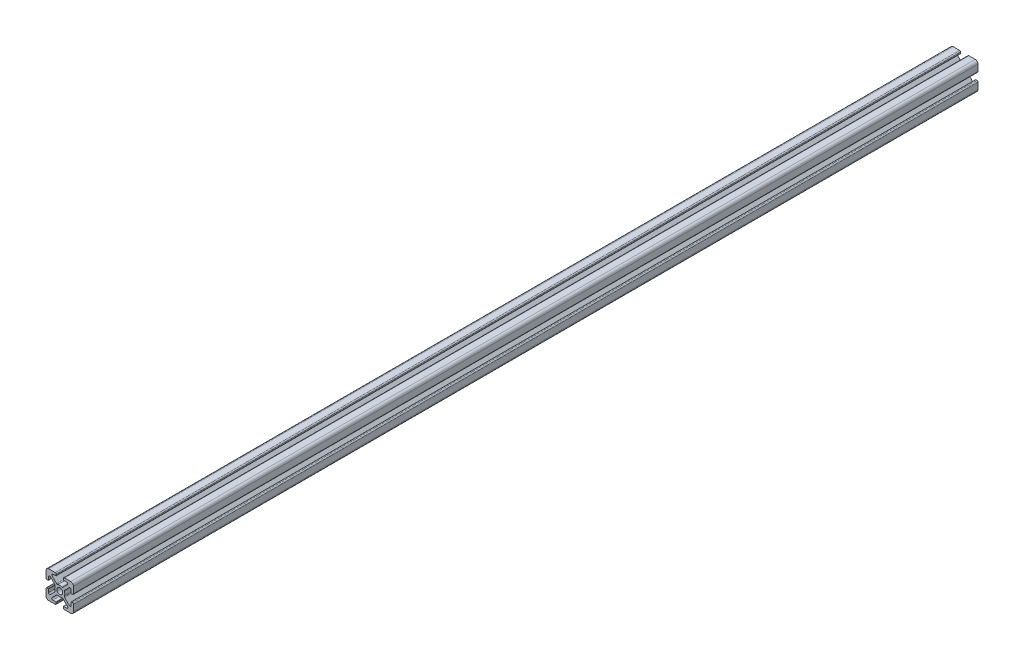
SolidWorks part; units mm, degrees
material "1060 Alloy"
ref_plane "Front Plane" through (0, 0, 0) normal (0, 0, 1) x (1, 0, 0)
ref_plane "Top Plane" through (0, 0, 0) normal (0, 1, 0) x (1, 0, 0)
ref_plane "Right Plane" through (0, 0, 0) normal (1, 0, 0) x (0, 0, -1)
sketch "PROFILE - DND" plane through (0, 0, 0) normal (0, 0, 1) x (1, 0, 0)
  line L0 (-5.0456, 8.2) -> (-2.825, 8.2)
  line L1 (-8, 10) -> (-3.3544, 10)
  line L5 (-10, 10) -> (0, 0) construction
  line L6 (-10, 10) -> (11.2313, -11.2313) construction
  line L15 (-5.5967, 6.8695) -> (-2.2618, 3.5346)
  line L18 (-9.3636, 10.6364) -> (11.8677, -10.5949) construction
  line L19 (0, 3.65) -> (0, 2.15)
  line L20 (-10, 8) -> (-10, 3.3544)
  line L21 (-9.2206, 2.575) -> (-8.45, 2.575)
  line L26 (-10, 8.2) -> (3.2269, 8.2) construction
  line L27 (-10, 8.2) -> (-22.2752, 8.2) construction
  line L28 (-22.2752, 8.2) -> (8.212, -7.6348) construction
  line L29 (3.2269, 8.2) -> (8.212, -7.6348) construction
  line L30 (-10, 0) -> (-3.65, 0) construction
  line L31 (0, 10) -> (0, 3.65) construction
  line L32 (-2.575, 9.2206) -> (-2.575, 8.45)
  line L37 (-2.575, 10) -> (-2.575, -10) construction
  line L39 (-8.2, 2.825) -> (-8.2, 5.0456)
  line L42 (-29.646, 10) -> (11.2313, -11.2313) construction
  line L44 (-10, 10) -> (4.5474, 10) construction
  line L47 (-10, 10) -> (-29.646, 10) construction
  line L50 (-6.8695, 5.5967) -> (-3.5346, 2.2618)
  line L55 (4.5474, 10) -> (11.2313, -11.2313) construction
  line L56 (0, 10) -> (0, -10) construction
  line L57 (-3.65, 0) -> (-2.15, 0)
  arc A0 (0, 2.15) -> (-2.15, 0) centre (0, 0) ccw
  arc A1 (0, 3.65) -> (-1.4097, 3.3668) centre (0, 0) ccw
  arc A3 (-5.5967, 6.8695) -> (-5.0456, 8.2) centre (-5.0456, 7.4206) cw
  arc A4 (-8.2, 5.0456) -> (-6.8695, 5.5967) centre (-7.4206, 5.0456) cw
  arc A5 (-2.2618, 3.5346) -> (-1.4097, 3.3668) centre (-1.7107, 4.0857) ccw
  arc A6 (-3.5346, 2.2618) -> (-3.3668, 1.4097) centre (-4.0857, 1.7107) cw
  arc A7 (-8, 10) -> (-10, 8) centre (-8, 8) ccw
  arc A8 (-2.575, 9.2206) -> (-3.3544, 10) centre (-3.3544, 9.2206) ccw
  arc A9 (-10, 3.3544) -> (-9.2206, 2.575) centre (-9.2206, 3.3544) ccw
  arc A10 (-2.575, 8.45) -> (-2.825, 8.2) centre (-2.825, 8.45) cw
  arc A11 (-8.45, 2.575) -> (-8.2, 2.825) centre (-8.45, 2.825) ccw
  arc A12 (-3.3668, 1.4097) -> (-3.65, 0) centre (0, 0) ccw
  point P71 (-5.825, 7.4206)
  dimension "D3" = 4.3
  dimension "D9" = 0.7794
  dimension "D10" = 2
  dimension "D13" = 0.25
  dimension "D2" = 7.3
  dimension "D4" = 6.35
  dimension "D5" = 5.15
  dimension "D6" = 11.65
  dimension "D8" = 1.8
  dimension "D7" = 20
  dimension "D1" = 1.8
sketch "Sketch2" plane through (0, 0, 0) normal (0, 0, 1) x (1, 0, 0)
  line L25 (-5.0456, 8.2) -> (-2.825, 8.2) construction
  line L26 (-2.575, 9.2206) -> (-2.575, 8.45) construction
  line L27 (-8, 10) -> (-3.3544, 10) construction
  line L28 (-10, 8) -> (-10, 3.3544) construction
  line L29 (-9.2206, 2.575) -> (-8.45, 2.575) construction
  line L30 (-8.2, 2.825) -> (-8.2, 5.0456) construction
  line L31 (-6.8695, 5.5967) -> (-3.5346, 2.2618) construction
  line L33 (-3.65, 0) -> (-2.15, 0) construction
  line L34 (0, 3.65) -> (0, 2.15) construction
  line L36 (-5.5967, 6.8695) -> (-2.2618, 3.5346) construction
  line L37 (-5.0456, 8.2) -> (-2.825, 8.2)
  line L38 (-2.575, 9.2206) -> (-2.575, 8.45)
  line L39 (-8, 10) -> (-3.3544, 10)
  line L40 (-10, 8) -> (-10, 3.3544)
  line L41 (-9.2206, 2.575) -> (-8.45, 2.575)
  line L42 (-8.2, 2.825) -> (-8.2, 5.0456)
  line L43 (-6.8695, 5.5967) -> (-3.5346, 2.2618)
  line L45 (-3.65, 0) -> (-2.15, 0)
  line L46 (0, 3.65) -> (0, 2.15)
  line L48 (-5.5967, 6.8695) -> (-2.2618, 3.5346)
  arc A0 (0, 3.65) -> (-1.4097, 3.3668) centre (0, 0) ccw construction
  arc A1 (-3.3668, 1.4097) -> (-3.65, 0) centre (0, 0) ccw construction
  arc A2 (0, 3.65) -> (-1.4097, 3.3668) centre (0, 0) ccw
  arc A3 (-3.3668, 1.4097) -> (-3.65, 0) centre (0, 0) ccw
  arc A20 (-5.0456, 8.2) -> (-5.5967, 6.8695) centre (-5.0456, 7.4206) ccw construction
  arc A21 (-2.825, 8.2) -> (-2.575, 8.45) centre (-2.825, 8.45) ccw construction
  arc A22 (-2.575, 9.2206) -> (-3.3544, 10) centre (-3.3544, 9.2206) ccw construction
  arc A23 (-8, 10) -> (-10, 8) centre (-8, 8) ccw construction
  arc A24 (-10, 3.3544) -> (-9.2206, 2.575) centre (-9.2206, 3.3544) ccw construction
  arc A25 (-8.45, 2.575) -> (-8.2, 2.825) centre (-8.45, 2.825) ccw construction
  arc A26 (-6.8695, 5.5967) -> (-8.2, 5.0456) centre (-7.4206, 5.0456) ccw construction
  arc A27 (-3.3668, 1.4097) -> (-3.5346, 2.2618) centre (-4.0857, 1.7107) ccw construction
  arc A28 (0, 2.15) -> (-2.15, 0) centre (0, 0) ccw construction
  arc A29 (-2.2618, 3.5346) -> (-1.4097, 3.3668) centre (-1.7107, 4.0857) ccw construction
  arc A30 (-5.0456, 8.2) -> (-5.5967, 6.8695) centre (-5.0456, 7.4206) ccw
  arc A31 (-2.825, 8.2) -> (-2.575, 8.45) centre (-2.825, 8.45) ccw
  arc A32 (-2.575, 9.2206) -> (-3.3544, 10) centre (-3.3544, 9.2206) ccw
  arc A33 (-8, 10) -> (-10, 8) centre (-8, 8) ccw
  arc A34 (-10, 3.3544) -> (-9.2206, 2.575) centre (-9.2206, 3.3544) ccw
  arc A35 (-8.45, 2.575) -> (-8.2, 2.825) centre (-8.45, 2.825) ccw
  arc A36 (-6.8695, 5.5967) -> (-8.2, 5.0456) centre (-7.4206, 5.0456) ccw
  arc A37 (-3.3668, 1.4097) -> (-3.5346, 2.2618) centre (-4.0857, 1.7107) ccw
  arc A38 (0, 2.15) -> (-2.15, 0) centre (0, 0) ccw
  arc A39 (-2.2618, 3.5346) -> (-1.4097, 3.3668) centre (-1.7107, 4.0857) ccw
extrude "Boss-Extrude1" add sketch "Sketch2" along normal blind 657
pattern_circular "CirPattern1" count 4 over 360 about axis through (0, 0, 657) along (0, 0, -1) of "Boss-Extrude1"
sketch "Sketch7" plane through (0, 0, 0) normal (0, 0, 1) x (1, 0, 0)
  line L0 (8.2, 5.0456) -> (8.2, 2.825) construction
  line L1 (8.2, 3.9353) -> (10, 3.9353)
  line L2 (8.2, 3.9353) -> (8.2, -3.9353)
  line L3 (8.2, -3.9353) -> (10, -3.9353)
  line L4 (10, 3.9353) -> (10, -3.9353)
  line L5 (8.2, -2.825) -> (8.2, -5.0456) construction
  line L6 (10, 3.3544) -> (10, 8) construction
extrude "Boss-Extrude3" [suppressed] add sketch "Sketch7" along normal up to vertex
sketch "Sketch8" plane through (0, 0, 0) normal (0, 0, 1) x (1, 0, 0)
  line L1 (-3.9353, 10) -> (3.9353, 10)
  line L2 (-3.9353, 10) -> (-3.9353, 8.2)
  line L3 (-3.9353, 8.2) -> (3.9353, 8.2)
  line L4 (3.9353, 10) -> (3.9353, 8.2)
  line L5 (-3.3544, 10) -> (-8, 10) construction
  line L6 (-5.0456, 8.2) -> (-2.825, 8.2) construction
  line L7 (2.825, 8.2) -> (5.0456, 8.2) construction
extrude "Boss-Extrude4" [suppressed] add sketch "Sketch8" along normal up to vertex
sketch "Sketch9" [suppressed] plane through (0, 0, 0) normal (0, 0, 1) x (1, 0, 0)
  line L0 (-8.2, -5.0456) -> (-8.2, -2.825) construction
  line L1 (-10, 3.9353) -> (-8.2, 3.9353)
  line L2 (-10, 3.9353) -> (-10, -3.9353)
  line L3 (-10, -3.9353) -> (-8.2, -3.9353)
  line L4 (-8.2, 3.9353) -> (-8.2, -3.9353)
  line L5 (-10, -3.3544) -> (-10, -8) construction
  line L6 (-8.2, 2.825) -> (-8.2, 5.0456) construction
extrude "Boss-Extrude5" [suppressed] add sketch "Sketch9" along normal up to vertex
pattern_linear "LPattern1" [suppressed] count 2 spacing 20 of bodies 102
sketch "Sketch4" [suppressed] plane through (0, 0, 0) normal (0, 0, 1) x (1, 0, 0)
  line L0 (8, 10) -> (12, 10)
  line L1 (8, -10) -> (12, -10)
  arc A0 (10, 8) -> (8, 10) centre (8, 8) ccw construction
  arc A1 (12, 10) -> (10, 8) centre (12, 8) ccw construction
  arc A2 (10, 8) -> (8, 10) centre (8, 8) ccw
  arc A3 (12, 10) -> (10, 8) centre (12, 8) ccw
  arc A4 (8, -10) -> (10, -8) centre (8, -8) ccw construction
  arc A5 (10, -8) -> (12, -10) centre (12, -8) ccw construction
  arc A6 (8, -10) -> (10, -8) centre (8, -8) ccw
  arc A7 (10, -8) -> (12, -10) centre (12, -8) ccw
extrude "Boss-Extrude2" [suppressed] add sketch "Sketch4" along normal up to vertex
sketch "Sketch3" [suppressed] plane through (0, 0, 0) normal (0, 0, 1) x (1, 0, 0)
  line L1 (9.4728, 8.2) -> (10.5272, 8.2) construction
  line L3 (9.4728, -8.2) -> (10.5272, -8.2) construction
  line L5 (3.5346, 2.2618) -> (6.8695, 5.5967) construction
  line L6 (13.1305, 5.5967) -> (16.4654, 2.2618) construction
  line L8 (2.825, 8.2) -> (5.0456, 8.2) construction
  line L9 (6.8695, -5.5967) -> (3.5346, -2.2618) construction
  line L10 (16.4654, -2.2618) -> (13.1305, -5.5967) construction
  line L11 (13.1305, -5.5967) -> (13.1305, 5.5967)
  line L12 (13.1305, 5.5967) -> (10.9, 7.8272)
  line L13 (9.1, 7.8272) -> (6.8695, 5.5967)
  line L14 (6.8695, 5.5967) -> (6.8695, -5.5967)
  line L15 (6.8695, -5.5967) -> (9.1, -7.8272)
  line L16 (10.9, -7.8272) -> (13.1305, -5.5967)
  line L17 (5.0456, -8.2) -> (2.825, -8.2) construction
  arc A0 (10.9, 7.8272) -> (9.1, 7.8272) centre (10, 6.9272) ccw
  arc A1 (9.1, -7.8272) -> (10.9, -7.8272) centre (10, -6.9272) ccw
  dimension "D2" = 1.0544
  dimension "D3" = 16.4
extrude "Cut-Extrude3" [suppressed] cut sketch "Sketch3" along normal up to vertex
pattern_linear "LPattern7" [suppressed] count 2 spacing 20 of bodies 110
sketch "Sketch5" [suppressed] plane through (0, 0, 0) normal (0, 0, 1) x (1, 0, 0)
  line L0 (9.1, 7.8272) -> (6.8695, 5.5967) construction
  line L1 (13.1305, 5.5967) -> (10.9, 7.8272) construction
  line L2 (13.1305, -5.5967) -> (13.1305, 5.5967) construction
  line L3 (10.9, -7.8272) -> (13.1305, -5.5967) construction
  line L4 (6.8695, -5.5967) -> (9.1, -7.8272) construction
  line L5 (6.8695, 5.5967) -> (6.8695, -5.5967) construction
  line L6 (9.1, 7.8272) -> (6.8695, 5.5967) construction
  line L7 (13.1305, 5.5967) -> (10.9, 7.8272) construction
  line L8 (13.1305, -5.5967) -> (13.1305, 5.5967) construction
  line L9 (10.9, -7.8272) -> (13.1305, -5.5967) construction
  line L10 (6.8695, -5.5967) -> (9.1, -7.8272) construction
  line L11 (6.8695, 5.5967) -> (6.8695, -5.5967) construction
  line L12 (26.8695, 5.5967) -> (26.8695, -5.5967)
  line L13 (26.8695, -5.5967) -> (29.1, -7.8272)
  line L14 (30.9, -7.8272) -> (33.1305, -5.5967)
  line L15 (33.1305, -5.5967) -> (33.1305, 5.5967)
  line L16 (33.1305, 5.5967) -> (30.9, 7.8272)
  line L17 (29.1, 7.8272) -> (26.8695, 5.5967)
  arc A0 (10.9, 7.8272) -> (9.1, 7.8272) centre (10, 6.9272) ccw construction
  arc A1 (9.1, -7.8272) -> (10.9, -7.8272) centre (10, -6.9272) ccw construction
  arc A2 (10.9, 7.8272) -> (9.1, 7.8272) centre (10, 6.9272) ccw construction
  arc A3 (9.1, -7.8272) -> (10.9, -7.8272) centre (10, -6.9272) ccw construction
  arc A4 (29.1, -7.8272) -> (30.9, -7.8272) centre (30, -6.9272) ccw
  arc A5 (30.9, 7.8272) -> (29.1, 7.8272) centre (30, 6.9272) ccw
  dimension "D2" = 20
  dimension "D1" = 2
extrude "Cut-Extrude5" [suppressed] cut sketch "Sketch5" along normal up to vertex
sketch "Sketch6" [suppressed] plane through (0, 0, 0) normal (0, 0, 1) x (1, 0, 0)
  line L0 (9.1, 7.8272) -> (6.8695, 5.5967) construction
  line L1 (13.1305, 5.5967) -> (10.9, 7.8272) construction
  line L2 (13.1305, -5.5967) -> (13.1305, 5.5967) construction
  line L3 (10.9, -7.8272) -> (13.1305, -5.5967) construction
  line L4 (6.8695, -5.5967) -> (9.1, -7.8272) construction
  line L5 (6.8695, 5.5967) -> (6.8695, -5.5967) construction
  line L6 (9.1, 7.8272) -> (6.8695, 5.5967) construction
  line L7 (13.1305, 5.5967) -> (10.9, 7.8272) construction
  line L8 (13.1305, -5.5967) -> (13.1305, 5.5967) construction
  line L9 (10.9, -7.8272) -> (13.1305, -5.5967) construction
  line L10 (6.8695, -5.5967) -> (9.1, -7.8272) construction
  line L11 (6.8695, 5.5967) -> (6.8695, -5.5967) construction
  line L12 (49.1, 7.8272) -> (46.8695, 5.5967)
  line L13 (46.8695, 5.5967) -> (46.8695, -5.5967)
  line L14 (46.8695, -5.5967) -> (49.1, -7.8272)
  line L15 (50.9, -7.8272) -> (53.1305, -5.5967)
  line L16 (53.1305, -5.5967) -> (53.1305, 5.5967)
  line L17 (53.1305, 5.5967) -> (50.9, 7.8272)
  arc A0 (10.9, 7.8272) -> (9.1, 7.8272) centre (10, 6.9272) ccw construction
  arc A1 (9.1, -7.8272) -> (10.9, -7.8272) centre (10, -6.9272) ccw construction
  arc A2 (10.9, 7.8272) -> (9.1, 7.8272) centre (10, 6.9272) ccw construction
  arc A3 (9.1, -7.8272) -> (10.9, -7.8272) centre (10, -6.9272) ccw construction
  arc A4 (49.1, -7.8272) -> (50.9, -7.8272) centre (50, -6.9272) ccw
  arc A5 (50.9, 7.8272) -> (49.1, 7.8272) centre (50, 6.9272) ccw
  dimension "D2" = 40
  dimension "D1" = 2
extrude "Cut-Extrude6" [suppressed] cut sketch "Sketch6" along normal up to vertex
sketch "Sketch10" [suppressed] plane through (0, 0, 0) normal (0, 0, 1) x (1, 0, 0)
  line L5 (-10, -8) -> (-8, -8)
  line L6 (-10, -8) -> (-10, -10)
  line L7 (-10, -10) -> (-8, -10)
  line L8 (-8, -8) -> (-8, -10)
  line L9 (8, 10) -> (10, 10)
  line L10 (8, 10) -> (8, 8)
  line L11 (8, 8) -> (10, 8)
  line L12 (10, 10) -> (10, 8)
extrude "Boss-Extrude6" [suppressed] add sketch "Sketch10" along normal up to vertex
sketch "Sketch11" [suppressed] plane through (0, 0, 0) normal (0, 0, 1) x (1, 0, 0)
  line L0 (3.5346, 2.2618) -> (6.8695, 5.5967) construction
  line L1 (3.5346, 2.2618) -> (9.1, 7.8272)
  line L2 (-5.5967, -6.8695) -> (-2.2618, -3.5346) construction
  line L3 (-7.8272, -9.1) -> (-2.2618, -3.5346)
  line L6 (-8.2, -10) -> (10, -10)
  line L7 (10, -10) -> (10, 8.2)
  line L10 (-5.0456, 8.2) -> (-2.825, 8.2) construction
  line L11 (-10, -10) -> (-3.3544, -10) construction
  line L12 (-8.2, 2.825) -> (-8.2, 5.0456) construction
  line L13 (10, -8) -> (10, -3.3544) construction
  arc A0 (3.3668, -1.4097) -> (3.3668, 1.4097) centre (0, 0) ccw construction
  arc A1 (3.5346, 2.2618) -> (3.3668, 1.4097) centre (4.0857, 1.7107) ccw construction
  arc A2 (-1.4097, -3.3668) -> (3.3668, 1.4097) centre (0, 0) ccw
  arc A3 (3.5346, 2.2618) -> (3.3668, 1.4097) centre (4.0857, 1.7107) ccw
  arc A4 (-1.4097, -3.3668) -> (-2.2618, -3.5346) centre (-1.7107, -4.0857) ccw construction
  arc A5 (-1.4097, -3.3668) -> (-2.2618, -3.5346) centre (-1.7107, -4.0857) ccw
  arc A13 (-8.2, -10) -> (-7.8272, -9.1) centre (-6.9272, -10) cw
  arc A14 (10, 8.2) -> (9.1, 7.8272) centre (10, 6.9272) ccw
extrude "Cut-Extrude7" [suppressed] cut sketch "Sketch11" along normal up to vertex
ref_axis "Axis1" [suppressed] through (10, -10, 0) along (0, 0, 1)
pattern_circular "CirPattern2" [suppressed] count 4 over 360 about axis through (10, -10, 0) along (0, 0, 1) of bodies 122
combine bodies "Combine1" [suppressed] bodies to combine 122 126 125 123
pattern_linear "LPattern8" [suppressed] count 2 spacing 40 count 2 spacing 20 of bodies 127
sketch "Sketch12" [suppressed] plane through (0, 0, 0) normal (0, 0, 1) x (1, 0, 0)
  line L0 (28, 10) -> (32, 10)
  line L1 (50, -8) -> (50, -12)
  line L2 (28, -30) -> (32, -30)
  line L3 (30, -12) -> (30, -8) construction
  line L4 (30, -12) -> (30, -8)
  arc A0 (32, 10) -> (30, 8) centre (32, 8) ccw construction
  arc A1 (30, 8) -> (28, 10) centre (28, 8) ccw construction
  arc A2 (32, 10) -> (30, 8) centre (32, 8) ccw
  arc A3 (30, 8) -> (28, 10) centre (28, 8) ccw
  arc A4 (50, -12) -> (48, -10) centre (48, -12) ccw construction
  arc A5 (48, -10) -> (50, -8) centre (48, -8) ccw construction
  arc A6 (50, -12) -> (48, -10) centre (48, -12) ccw
  arc A7 (48, -10) -> (50, -8) centre (48, -8) ccw
  arc A8 (30, -28) -> (32, -30) centre (32, -28) ccw construction
  arc A9 (28, -30) -> (30, -28) centre (28, -28) ccw construction
  arc A10 (30, -28) -> (32, -30) centre (32, -28) ccw
  arc A11 (28, -30) -> (30, -28) centre (28, -28) ccw
  arc A12 (32, -10) -> (30, -12) centre (32, -12) ccw construction
  arc A13 (30, -8) -> (32, -10) centre (32, -8) ccw construction
  arc A14 (32, -10) -> (30, -12) centre (32, -12) ccw
  arc A15 (30, -8) -> (32, -10) centre (32, -8) ccw
  point P21 (30, -10)
extrude "Boss-Extrude7" [suppressed] add sketch "Sketch12" along normal up to vertex
ref_axis "Axis2" [suppressed] through (30, -10, 0) along (0, 0, 1)
sketch "Sketch13" [suppressed] plane through (0, 0, 0) normal (0, 0, 1) x (1, 0, 0)
  line L0 (36.4654, -2.2618) -> (33.1305, -5.5967) construction
  line L1 (26.8695, -5.5967) -> (23.5346, -2.2618) construction
  line L2 (23.5346, 2.2618) -> (26.8695, 5.5967) construction
  line L3 (33.1305, 5.5967) -> (36.4654, 2.2618) construction
  line L4 (33.1305, -5.5967) -> (30.9, -7.8272)
  line L5 (29.1, -7.8272) -> (26.8695, -5.5967)
  line L6 (26.8695, 5.5967) -> (29.1, 7.8272)
  line L7 (30.9, 7.8272) -> (33.1305, 5.5967)
  line L8 (26.8695, 5.5967) -> (26.8695, -5.5967)
  line L9 (33.1305, 5.5967) -> (33.1305, -5.5967)
  line L10 (-5.0456, 8.2) -> (-2.825, 8.2) construction
  arc A0 (30.9, -7.8272) -> (29.1, -7.8272) centre (30, -6.9272) cw
  arc A1 (30.9, 7.8272) -> (29.1, 7.8272) centre (30, 6.9272) ccw
extrude "Cut-Extrude8" [suppressed] cut sketch "Sketch13" along normal up to vertex
pattern_circular "CirPattern3" [suppressed] count 3 every 90 about axis through (30, -10, 0) along (0, 0, 1) reverse direction yes of bodies 135
sketch "Sketch14" [suppressed] plane through (0, 0, 0) normal (0, 0, 1) x (1, 0, 0)
  line L0 (-5.0456, 8.2) -> (-2.825, 8.2) construction
  line L4 (-2.575, 9.2206) -> (-2.575, 8.45) construction
  line L5 (-8, 10) -> (-3.3544, 10) construction
  line L6 (-10, 8) -> (-10, 3.3544) construction
  line L7 (0, 3.65) -> (0, 10) construction
  line L8 (-9.2206, 2.575) -> (-8.45, 2.575) construction
  line L9 (-8.2, 2.825) -> (-8.2, 5.0456) construction
  line L10 (-6.8695, 5.5967) -> (-3.5346, 2.2618) construction
  line L11 (-3.65, 0) -> (-2.15, 0) construction
  line L12 (0, 3.65) -> (0, 2.15) construction
  line L13 (-5.5967, 6.8695) -> (-2.2618, 3.5346) construction
  line L14 (-5.0456, 8.2) -> (-2.825, 8.2) construction
  line L15 (-2.575, 9.2206) -> (-2.575, 8.45) construction
  line L16 (-8, 10) -> (-3.3544, 10) construction
  line L17 (-10, 8) -> (-10, 3.3544) construction
  line L18 (-9.2206, 2.575) -> (-8.45, 2.575) construction
  line L19 (-8.2, 2.825) -> (-8.2, 5.0456) construction
  line L20 (-6.8695, 5.5967) -> (-3.5346, 2.2618) construction
  line L21 (-3.65, 0) -> (-2.15, 0)
  line L22 (0, 3.65) -> (0, 2.15)
  line L23 (-5.5967, 6.8695) -> (-2.2618, 3.5346) construction
  line L24 (8, 10) -> (3.3544, 10)
  line L25 (2.575, 9.2206) -> (2.575, 8.45)
  line L26 (5.0456, 8.2) -> (2.825, 8.2)
  line L27 (5.5967, 6.8695) -> (2.2618, 3.5346)
  line L28 (-10, 0) -> (-3.65, 0) construction
  line L29 (-10, 0) -> (-3.65, 0) construction
  line L30 (-10, -8) -> (-10, -3.3544)
  line L31 (-9.2206, -2.575) -> (-8.45, -2.575)
  line L32 (-8.2, -2.825) -> (-8.2, -5.0456)
  line L33 (-6.8695, -5.5967) -> (-3.5346, -2.2618)
  line L34 (-8, -8) -> (8, 8) construction
  line L35 (6.7872, 5.5144) -> (3.3989, 2.1261)
  line L36 (-5.2021, -3.9293) -> (-3.9293, -5.2021) construction
  line L38 (-5.5144, -6.7872) -> (-2.1261, -3.3989)
  arc A0 (-7.7791, -9.9878) -> (9.9878, 7.7791) centre (-10, 10) ccw
  arc A1 (-3.3668, 1.4097) -> (-3.65, 0) centre (0, 0) ccw construction
  arc A2 (0, 2.15) -> (-2.15, 0) centre (0, 0) ccw construction
  arc A8 (-5.0456, 8.2) -> (-5.5967, 6.8695) centre (-5.0456, 7.4206) ccw construction
  arc A9 (-2.825, 8.2) -> (-2.575, 8.45) centre (-2.825, 8.45) ccw construction
  arc A10 (-2.575, 9.2206) -> (-3.3544, 10) centre (-3.3544, 9.2206) ccw construction
  arc A11 (-8, 10) -> (-10, 8) centre (-8, 8) ccw construction
  arc A12 (-10, 3.3544) -> (-9.2206, 2.575) centre (-9.2206, 3.3544) ccw construction
  arc A13 (-8.45, 2.575) -> (-8.2, 2.825) centre (-8.45, 2.825) ccw construction
  arc A14 (-6.8695, 5.5967) -> (-8.2, 5.0456) centre (-7.4206, 5.0456) ccw construction
  arc A15 (-3.3668, 1.4097) -> (-3.5346, 2.2618) centre (-4.0857, 1.7107) ccw construction
  arc A16 (0, 3.65) -> (-1.4097, 3.3668) centre (0, 0) ccw construction
  arc A17 (-2.2618, 3.5346) -> (-1.4097, 3.3668) centre (-1.7107, 4.0857) ccw construction
  arc A18 (-5.0456, 8.2) -> (-5.5967, 6.8695) centre (-5.0456, 7.4206) ccw construction
  arc A19 (-2.825, 8.2) -> (-2.575, 8.45) centre (-2.825, 8.45) ccw construction
  arc A20 (-2.575, 9.2206) -> (-3.3544, 10) centre (-3.3544, 9.2206) ccw construction
  arc A21 (-8, 10) -> (-10, 8) centre (-8, 8) ccw construction
  arc A22 (-10, 3.3544) -> (-9.2206, 2.575) centre (-9.2206, 3.3544) ccw construction
  arc A23 (-8.45, 2.575) -> (-8.2, 2.825) centre (-8.45, 2.825) ccw construction
  arc A24 (-6.8695, 5.5967) -> (-8.2, 5.0456) centre (-7.4206, 5.0456) ccw construction
  arc A25 (-3.3668, 1.4097) -> (-3.5346, 2.2618) centre (-4.0857, 1.7107) ccw construction
  arc A26 (-3.65, 0) -> (-3.3668, -1.4097) centre (0, 0) ccw
  arc A27 (-2.15, 0) -> (0, 2.15) centre (0, 0) ccw
  arc A28 (1.4097, 3.3668) -> (0, 3.65) centre (0, 0) ccw
  arc A29 (-2.2618, 3.5346) -> (-1.4097, 3.3668) centre (-1.7107, 4.0857) ccw construction
  arc A30 (2.575, 9.2206) -> (3.3544, 10) centre (3.3544, 9.2206) cw
  arc A31 (2.825, 8.2) -> (2.575, 8.45) centre (2.825, 8.45) cw
  arc A32 (5.0456, 8.2) -> (5.5967, 6.8695) centre (5.0456, 7.4206) cw
  arc A33 (2.2618, 3.5346) -> (1.4097, 3.3668) centre (1.7107, 4.0857) cw
  arc A34 (-10, -3.3544) -> (-9.2206, -2.575) centre (-9.2206, -3.3544) cw
  arc A35 (-8.45, -2.575) -> (-8.2, -2.825) centre (-8.45, -2.825) cw
  arc A36 (-6.8695, -5.5967) -> (-8.2, -5.0456) centre (-7.4206, -5.0456) cw
  arc A37 (-3.3668, -1.4097) -> (-3.5346, -2.2618) centre (-4.0857, -1.7107) cw
  arc A38 (8, 10) -> (9.9878, 7.7791) centre (8, 8) cw
  arc A39 (-10, -8) -> (-7.7791, -9.9878) centre (-8, -8) ccw
  arc A40 (-1.559, -3.3003) -> (0.8474, -3.5503) centre (0, 0) ccw
  arc A41 (4.4307, -1.2712) -> (7.622, 5.025) centre (-10, 10) ccw
  arc A42 (-7.9779, -8.1988) -> (8.1988, 7.9779) centre (-10, 10) ccw construction
  arc A43 (3.5503, -0.8474) -> (3.3003, 1.559) centre (0, 0) ccw
  arc A44 (0.8474, -3.5503) -> (1.2712, -4.4307) centre (0.9634, -4.0366) cw
  arc A45 (3.3989, 2.1261) -> (3.3003, 1.559) centre (3.7524, 1.7725) ccw
  arc A46 (-5.025, -7.622) -> (1.2712, -4.4307) centre (-10, 10) ccw
  arc A47 (-1.559, -3.3003) -> (-2.1261, -3.3989) centre (-1.7725, -3.7524) ccw
  arc A48 (6.7872, 5.5144) -> (7.622, 5.025) centre (7.1408, 5.1609) cw
  arc A49 (-5.5144, -6.7872) -> (-5.025, -7.622) centre (-5.1609, -7.1408) ccw
  arc A50 (4.4307, -1.2712) -> (3.5503, -0.8474) centre (4.0366, -0.9634) cw
  point P75 (-4.5657, -4.5657)
  point P93 (-1.8649, -3.1376)
  dimension "D3" = 0.5
  dimension "D1" = 1.8
extrude "Boss-Extrude8" [suppressed] add sketch "Sketch14" along normal up to vertex
mirror "Mirror1" [suppressed] about plane through (0, 0, 0) normal (1, 0, 0)
pattern_linear "LPattern9" [suppressed] count 2 spacing 20 of bodies 138
sketch "Sketch15" [suppressed] plane through (0, 0, 0) normal (0, 0, 1) x (1, 0, 0)
  line L1 (-3.65, 0) -> (-2.15, 0) construction
  line L2 (-10, 0) -> (30, 0)
  line L3 (-10, 0) -> (-10, 5.825)
  line L4 (-10, 5.825) -> (30, 5.825)
  line L5 (30, 0) -> (30, 5.825)
  line L6 (30, 8) -> (30, 3.3544) construction
  line L7 (-10, 8) -> (-10, 3.3544) construction
  line L18 (8, 10) -> (12, 10)
  arc A4 (-6.8695, 5.5967) -> (-8.2, 5.0456) centre (-7.4206, 5.0456) ccw construction
  arc A17 (12, 10) -> (10, 8) centre (12, 8) ccw construction
  arc A18 (10, 8) -> (8, 10) centre (8, 8) ccw construction
  arc A19 (12, 10) -> (10, 8) centre (12, 8) ccw
  arc A20 (10, 8) -> (8, 10) centre (8, 8) ccw
extrude "Boss-Extrude9" [suppressed] add sketch "Sketch15" along normal up to vertex
sketch "Sketch16" [suppressed] plane through (0, 0, 0) normal (0, 0, 1) x (1, 0, 0)
  line L6 (4.5522, 5.825) -> (-4.5522, 5.825) construction
  line L7 (-4.5522, 5.825) -> (-5.5967, 6.8695) construction
  line L8 (4.5522, 5.825) -> (-4.5522, 5.825)
  line L9 (-4.5522, 5.825) -> (-2.2618, 3.5346)
  line L13 (4.5522, 5.825) -> (5.5967, 6.8695) construction
  line L17 (4.5522, 5.825) -> (2.2618, 3.5346)
  line L18 (-8.2, 2.825) -> (-8.2, 5.0456) construction
  line L19 (-6.8695, 5.5967) -> (-3.5346, 2.2618) construction
  line L20 (10, 10) -> (10, 8.2) construction
  line L21 (3.3544, 10) -> (16.6456, 10) construction
  line L22 (-10, 0) -> (30, 0) construction
  line L23 (5.0456, 8.2) -> (10, 8.2) construction
  line L24 (5.0456, 8.2) -> (2.825, 8.2) construction
  line L25 (9.1, 7.8272) -> (5.2456, 3.9728)
  line L26 (6.1456, 1.8) -> (10, 1.8)
  line L27 (10, 1.8) -> (10, 0) construction
  line L28 (5.825, 4.5522) -> (3.5346, 2.2618) construction
  line L29 (10, 8.2) -> (10, 1.8)
  arc A0 (-2.2618, 3.5346) -> (2.2618, 3.5346) centre (0, 5.7964) ccw
  circle A2 centre (-6.6983, 3.3017) radius 1.5017
  arc A3 (5.2456, 3.9728) -> (6.1456, 1.8) centre (6.1456, 3.0728) ccw
  arc A4 (10, 8.2) -> (9.1, 7.8272) centre (10, 6.9272) ccw
  point P22 (-6.6983, 1.8)
  dimension "D1" = 1.8
  dimension "D2" = 1.8
extrude "Cut-Extrude9" [suppressed] cut sketch "Sketch16" along normal up to vertex
mirror "Mirror2" [suppressed]
fillet "Fillet1" [suppressed] radius 1
